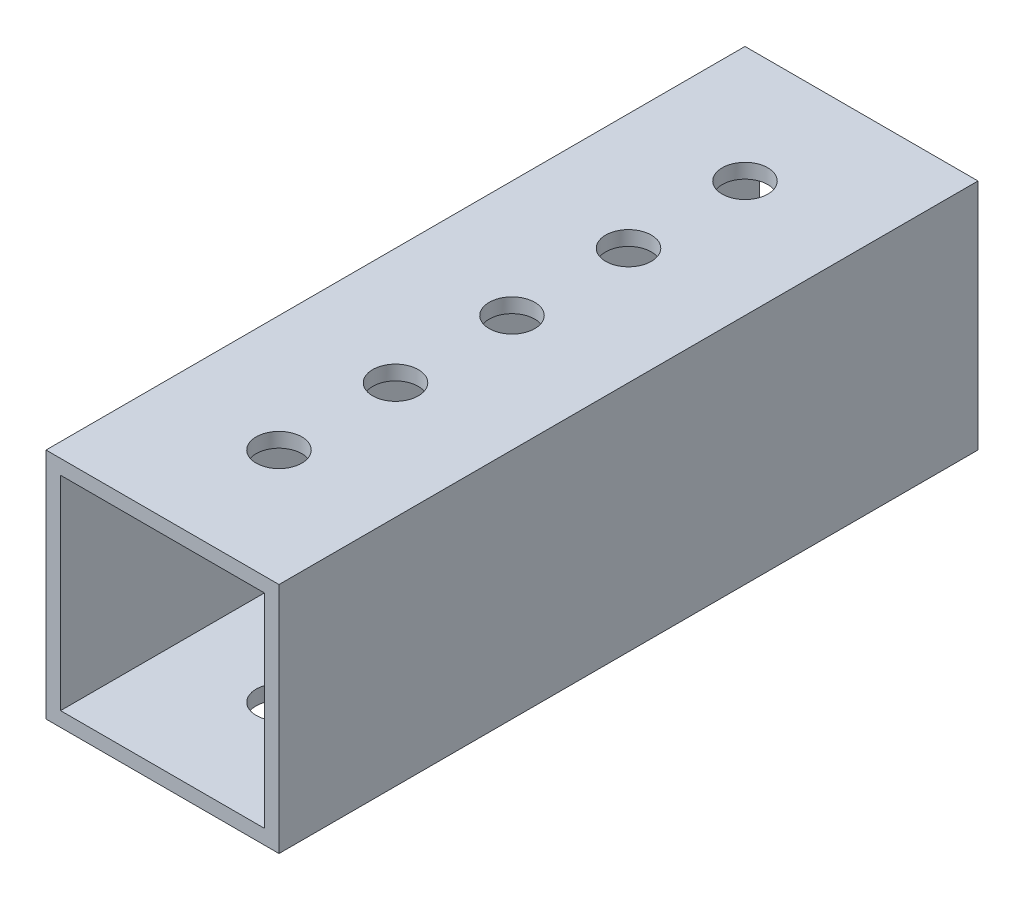
SolidWorks part; units mm, degrees
material "6061-T6 (SS)"
ref_plane "Front Plane" through (0, 0, 0) normal (0, 0, 1) x (1, 0, 0)
ref_plane "Top Plane" through (0, 0, 0) normal (0, 1, 0) x (1, 0, 0)
ref_plane "Right Plane" through (0, 0, 0) normal (1, 0, 0) x (0, 0, -1)
sketch "Sketch1" plane through (0, 0, 0) normal (0, 0, 1) x (1, 0, 0)
  line L1 (-12.7, -12.7) -> (12.7, -12.7)
  line L2 (-12.7, -12.7) -> (-12.7, 12.7)
  line L3 (-12.7, 12.7) -> (12.7, 12.7)
  line L4 (12.7, -12.7) -> (12.7, 12.7)
  line L5 (-12.7, -12.7) -> (12.7, 12.7) construction
  line L6 (-12.7, 12.7) -> (12.7, -12.7) construction
  point P0 (0, 0)
  dimension "D1" = 25.4
extrude "Boss-Extrude1" add sketch "Sketch1" along normal mid plane 76.2
shell "Shell1" thickness 1.5875 removed face at (0, 0, -38.1) removed face at (0, 0, 38.1)
sketch "Sketch2" plane through (0, 0, 0) normal (0, 1, 0) x (1, 0, 0)
  line L0 (12.7, -38.1) -> (-12.7, -38.1) construction
  circle A0 centre (0, -25.4) radius 2.4892
  circle A2 centre (0, -12.7) radius 2.4892
  circle A3 centre (0, 0) radius 2.4892
  circle A4 centre (0, 12.7) radius 2.4892
  circle A5 centre (0, 25.4) radius 2.4892
  dimension "D1" = 4.9784
  dimension "D2" = 12.7
  dimension "D3" = 12.7
extrude "Cut-Extrude1" cut sketch "Sketch2" against normal through all both and the other way through all
